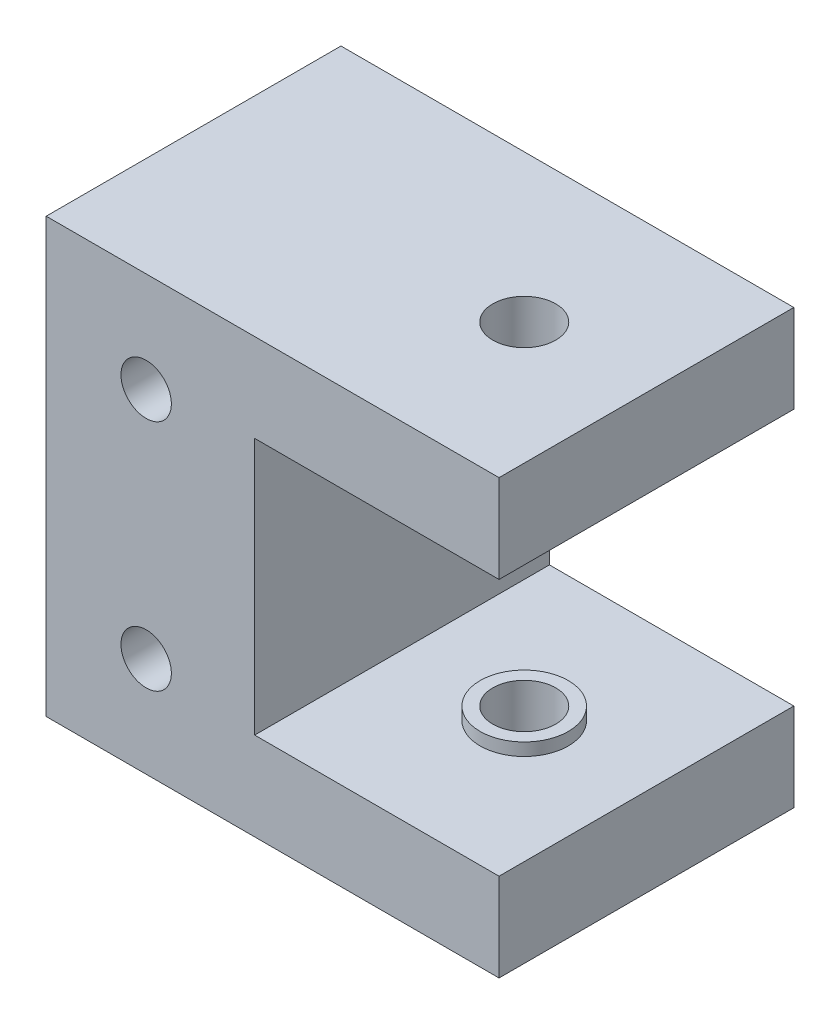
SolidWorks part; units mm, degrees
ref_plane "Front Plane" through (0, 0, 0) normal (0, 0, 1) x (1, 0, 0)
ref_plane "Top Plane" through (0, 0, 0) normal (0, 1, 0) x (1, 0, 0)
ref_plane "Right Plane" through (0, 0, 0) normal (1, 0, 0) x (0, 0, -1)
sketch "MainBlock" plane through (0, 0, 0) normal (0, 0, 1) x (1, 0, 0)
  line L0 (0, 0) -> (35.95, 0)
  line L1 (35.95, 0) -> (35.95, 7)
  line L2 (35.95, 7) -> (16.55, 7)
  line L3 (16.55, 7) -> (16.55, 27.4)
  line L4 (16.55, 27.4) -> (35.95, 27.4)
  line L5 (35.95, 27.4) -> (35.95, 34.4)
  line L6 (35.95, 34.4) -> (0, 34.4)
  line L7 (0, 34.4) -> (0, 0)
  circle A0 centre (7.9375, 26.4625) radius 2
  circle A1 centre (7.9375, 7.9375) radius 2
  dimension "D4" = 4
  dimension "D1" = 35.95
  dimension "D2" = 34.4
  dimension "D3" = 20.4
  dimension "D5" = 19.4
  dimension "D6" = 7.9375
  dimension "D7" = 7.9375
  dimension "D8" = 7.9375
extrude "MainBlockBoss-Extrude1" add sketch "MainBlock" along normal blind 23.4
sketch "TopHoleCut-Sketch2" plane through (0, 34.4, 0) normal (0, 1, 0) x (1, 0, 0)
  line L0 (35.95, 0) -> (0, 0) construction
  line L1 (0, -23.4) -> (0, 0) construction
  circle A0 centre (26.25, -11.7) radius 2.5
  dimension "D3" = 5
  dimension "D1" = 11.7
  dimension "D2" = 26.25
extrude "TopHoleCut-Extrude1" cut sketch "TopHoleCut-Sketch2" against normal blind 30
sketch "TopSpacerSketch4" plane through (0, 27.4, 0) normal (0, -1, 0) x (1, 0, 0)
  circle A0 centre (26.25, 11.7) radius 3.5
  circle A1 centre (26.25, 11.7) radius 2.5
  circle A2 centre (26.25, 11.7) radius 2.5 construction
  dimension "D1" = 7
extrude "TopSpacerBoss-Extrude2" add sketch "TopSpacerSketch4" along normal blind 1
sketch "LowerSpacerSketch5" plane through (0, 7, 0) normal (0, 1, 0) x (1, 0, 0)
  circle A0 centre (26.25, -11.7) radius 2.5
  circle A1 centre (26.25, -11.7) radius 2.5 construction
  circle A2 centre (26.25, -11.7) radius 3.5
  circle A3 centre (26.25, -11.7) radius 3.5 construction
extrude "LowerSpacerBoss-Extrude3" add sketch "LowerSpacerSketch5" along normal blind 1
sketch "MountHoleBoreSketch1" plane through (0, 0, 0) normal (0, 0, -1) x (-1, 0, 0)
  line L1 (-4.0625, 26.4625) -> (-6, 29.8183)
  line L2 (-6, 29.8183) -> (-9.875, 29.8183)
  line L3 (-9.875, 29.8183) -> (-11.8125, 26.4625)
  line L4 (-11.8125, 26.4625) -> (-9.875, 23.1067)
  line L5 (-9.875, 23.1067) -> (-6, 23.1067)
  line L6 (-6, 23.1067) -> (-4.0625, 26.4625)
  line L7 (-4.0625, 7.9375) -> (-6, 11.2933)
  line L8 (-6, 11.2933) -> (-9.875, 11.2933)
  line L9 (-9.875, 11.2933) -> (-11.8125, 7.9375)
  line L10 (-11.8125, 7.9375) -> (-9.875, 4.5817)
  line L11 (-9.875, 4.5817) -> (-6, 4.5817)
  line L12 (-6, 4.5817) -> (-4.0625, 7.9375)
  circle A0 centre (-7.9375, 26.4625) radius 3.3558 construction
  circle A1 centre (-7.9375, 7.9375) radius 3.3558 construction
  dimension "D1" = 7.75
extrude "MountHoleBoreCut-Extrude1" cut sketch "MountHoleBoreSketch1" against normal blind 2
sketch "PushPinHoleSketch1" plane through (0, 0, 0) normal (0, -1, 0) x (1, 0, 0)
  circle A0 centre (26.25, 11.7) radius 1
  circle A1 centre (26.25, 11.7) radius 2.5 construction
  dimension "D1" = 2
extrude "PushPinHoleCut-Extrude1" cut sketch "PushPinHoleSketch1" against normal through all
equation "\"BeltTensionerWidth\"= \"MidRailToAlignWithGantryBlock\" + \"BeltTensionerInnerWidth\" / 2"
equation "\"BeltTensionerHeight\"= \"BeltTensionerInnerHeight\" + \"BeltTensionerUpperLowerWallThickness\" * 2"
equation "\"BeltTensionerDepth\"= \"BeltTensionerBackWallThickness\" + \"BeltTensionerInnerDepth\"'Equals 23.4"
equation "\"BeltTensionerUpperLowerWallThickness\"= 7mm"
equation "\"BeltTensionerInnerWidth\"= \"20TGT2PulleyDiameter\" + \"BeltTensionerSpaceBetweenPulleyAndWall\""
equation "\"BeltTensionerInnerHeight\"= \"20TGT2PulleyWidth\" * 2 + \"1mmSpacer\" * 3"
equation "\"BeltTensionerBackWallThickness\"= 4mm"
equation "\"BeltTensionerInnerDepth\"= \"20TGT2PulleyDiameter\" + \"BeltTensionerSpaceBetweenPulleyAndWall\""
equation "\"RailThickness\"= .125in'Spec"
equation "\"HoleOffsetFromEdge\"= \"RailThickness\" * 2.5"
equation "\"LinearGBWithRailDepth\"= 12.75mm'Spec"
equation "\"GABDistanceFromBackToFirstPulley\"= 13.5mm"
equation "\"MidRailToAlignWithGantryBlock\"= \"LinearGBWithRailDepth\" + \"GABDistanceFromBackToFirstPulley\"'All outside cogs must align"
equation "\"20TGT2PulleyDiameter\"= 17.9mm'Spec"
equation "\"BeltTensionerSpaceBetweenPulleyAndWall\"= 1.5mm"
equation "\"BeltTensionerMountingHoleDiameter\"= 4.0mm"
equation "\"BeltTensionerMountingHoleOffsetFromEdge\"= \"HoleOffsetFromEdge\""
equation "\"20TGT2PulleyWidth\"= 8.7mm'The STL of the Pulley in the diagram is a bit larger"
equation "\"1mmSpacer\"= 1mm"
equation "\"SteelShaft5mmHoleDiameter\"= 5mm"
equation "\"BeltTensionerMountingHoleOuterBoreDepth\"= 2mm"
equation "\"BeltTensionerMountingHoleOuterBoreDiameter\"= 7.75mm'From the100"
equation "\"7mmx1mmSpacerDiameter\"= 7mm"
equation "\"7mmx1mmSpacerHeight\"= 1mm"
equation "\"D1@MainBlock\" = \"BeltTensionerWidth\""
equation "\"D2@MainBlock\" = \"BeltTensionerHeight\""
equation "\"D3@MainBlock\" = \"BeltTensionerInnerHeight\""
equation "\"D4@MainBlock\" = \"BeltTensionerMountingHoleDiameter\""
equation "\"D5@MainBlock\" = \"BeltTensionerInnerWidth\""
equation "\"D6@MainBlock\"=\"BeltTensionerMountingHoleOffsetFromEdge\""
equation "\"D7@MainBlock\" = \"HoleOffsetFromEdge\""
equation "\"D8@MainBlock\" = \"HoleOffsetFromEdge\""
equation "\"D1@MainBlockBoss-Extrude1\" = \"BeltTensionerDepth\""
equation "\"D1@TopHoleCut-Sketch2\" = \"BeltTensionerDepth\" / 2"
equation "\"D2@TopHoleCut-Sketch2\" = \"MidRailToAlignWithGantryBlock\""
equation "\"D3@TopHoleCut-Sketch2\" = \"SteelShaft5mmHoleDiameter\""
equation "\"D1@TopSpacerSketch4\" = \"7mmx1mmSpacerDiameter\""
equation "\"D1@TopSpacerBoss-Extrude2\" = \"7mmx1mmSpacerHeight\""
equation "\"D1@LowerSpacerBoss-Extrude3\" = \"7mmx1mmSpacerHeight\""
equation "\"D1@MountHoleBoreSketch1\" = \"BeltTensionerMountingHoleOuterBoreDiameter\""
equation "\"D1@MountHoleBoreCut-Extrude1\" = \"BeltTensionerMountingHoleOuterBoreDepth\""
equation "\"StealPinPushHoleDiameter\"= 2mm"
equation "\"D1@PushPinHoleSketch1\" = \"StealPinPushHoleDiameter\""
